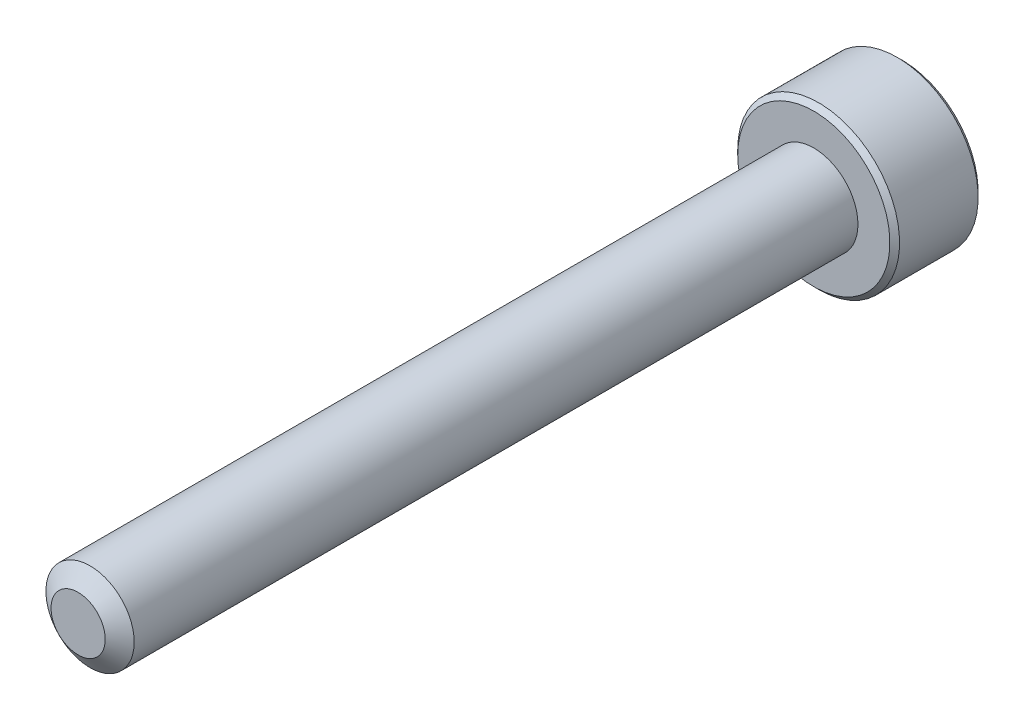
SolidWorks part; units mm, degrees
ref_plane "Front Plane" through (0, 0, 0) normal (0, 0, 1) x (1, 0, 0)
ref_plane "Top Plane" through (0, 0, 0) normal (0, 1, 0) x (1, 0, 0)
ref_plane "Right Plane" through (0, 0, 0) normal (1, 0, 0) x (0, 0, -1)
sketch "Sketch1" plane through (0, 0, 0) normal (0, 0, 1) x (1, 0, 0)
  circle A0 centre (0, 0) radius 1.5
  dimension "OD" = 3
extrude "Extrude1" add sketch "Sketch1" against normal blind 25
sketch "Sketch2" plane through (0, 0, 0) normal (0, 0, 1) x (1, 0, 0)
  circle A0 centre (0, 0) radius 1.5 construction
  circle A1 centre (0, 0) radius 1.5
curve "Helix/Spiral1" pitch 0.5 height 25.5 turns 51 parameters "pitch"=0.5
sketch "Sketch3" plane through (0, 0, 0) normal (1, 0, 0) x (0, 0, -1)
  line L0 (-0.4375, 1.5) -> (-0.25, 1.1752)
  line L1 (-0.25, 1.1752) -> (-0.1875, 1.1752)
  line L2 (-0.1875, 1.1752) -> (0, 1.5)
  line L3 (-0.4375, 1.5) -> (0, 1.5)
  line L4 (-0.2187, 1.5) -> (-0.2187, 1.1752) construction
  line L5 (-0.3437, 1.3376) -> (-0.0937, 1.3376) construction
  line L6 (0, 1.5) -> (0, -1.5) construction
  line L7 (0, -1.5) -> (25, -1.5) construction
  point P11 (2.25, -1.5)
  dimension "D1" = 0.0625
  dimension "D2" = 0.25
  dimension "D3" = 60
  dimension "D4" = 2.25
sweep "Cut-Sweep1" [suppressed] cut profiles "Sketch3" path "Helix/Spiral1"
sketch "Sketch4" plane through (0, 0, 0) normal (1, 0, 0) x (0, 0, -1)
  line L0 (0.4053, 1.5) -> (0, 0.9212)
  line L1 (0, 0.9212) -> (0, 1.5)
  line L2 (0.4053, 1.5) -> (0, 1.5)
  line L3 (-0.4375, 1.5) -> (0, 1.5) construction
  line L4 (0, 0) -> (7.0209, 0) construction
  dimension "D1" = 55
  dimension "D2" = 0.254
revolve "Cut-Revolve1" cut sketch "Sketch4" angle 360 about L4
sketch "Sketch5" [suppressed] plane through (0, 0, 0) normal (1, 0, 0) x (0, 0, -1)
  line L0 (25, -1.1822) -> (25, 1.0703) construction
  line L1 (25, 1.5) -> (18.1202, 1.5)
  line L2 (25, 1.5) -> (25, 0)
  line L3 (25, 0) -> (18, 0)
  line L4 (18, 1.1698) -> (18, 0)
  line L5 (18.1202, 1.5) -> (18, 1.1698)
  line L6 (0, 0) -> (9.9695, 0) construction
  point P3 (18, 1.5)
  point P10 (18, 1.5)
  dimension "D1" = 0.3302
  dimension "Thread min" = 18
  dimension "D3" = 20
revolve "partially thread" [suppressed] add sketch "Sketch5" angle 360 about L6
sketch "Sketch6" plane through (0, 0, -25) normal (0, 0, -1) x (-1, 0, 0)
  circle A0 centre (0, 0) radius 2.75
  dimension "head dia" = 5.5
extrude "Extrude2" add sketch "Sketch6" along normal blind 3
sketch "Sketch7" plane through (0, 0, -28) normal (0, 0, -1) x (-1, 0, 0)
  line L1 (0, 1.4434) -> (-1.25, 0.7217)
  line L2 (-1.25, 0.7217) -> (-1.25, -0.7217)
  line L3 (-1.25, -0.7217) -> (0, -1.4434)
  line L4 (0, -1.4434) -> (1.25, -0.7217)
  line L5 (1.25, -0.7217) -> (1.25, 0.7217)
  line L6 (1.25, 0.7217) -> (0, 1.4434)
  circle A0 centre (0, 0) radius 1.25 construction
  dimension "hex dia" = 2.5
extrude "Cut-Extrude1" cut sketch "Sketch7" against normal blind 1.875
sketch "Sketch8" plane through (0, 0, -28) normal (0, 0, -1) x (-1, 0, 0)
  circle A0 centre (0, 0) radius 1.4434
extrude "Cut-Extrude2" cut sketch "Sketch8" against normal through all draft 45
chamfer "Chamfer1" distance 0.165 angle 45 2 edges at (-2.75, 0, -28) (-2.75, 0, -25)
sketch "Sketch9" plane through (0, 0, 0) normal (1, 0, 0) x (0, 0, -1)
  line L0 (0, 1.5) -> (0, -1.5) construction
  line L1 (2.75, 1.5) -> (2.75, -1.5) construction
  dimension "D1" = 2.75
sketch "Sketch10" plane through (0, 0, 0) normal (1, 0, 0) x (0, 0, -1)
  line L0 (25, 1.5) -> (25, 0)
  line L1 (25, 1.5) -> (24.875, 1.5)
  line L2 (24.875, 1.5) -> (24.2537, 0)
  line L3 (25, 0) -> (24.2537, 0)
  line L4 (25, 2.585) -> (25, -2.585) construction
  dimension "D1" = 22.5
  dimension "D2" = 0.125
revolve "Revolve1" add sketch "Sketch10" angle 360 about L3
equation "\"D3@Helix/Spiral1\" = \"screw length@Extrude1\"+\"pitch@Helix/Spiral1\""
equation "\"D1@Sketch3\" = \"pitch@Helix/Spiral1\"*.125"
equation "\"D2@Sketch3\" = \"pitch@Helix/Spiral1\"*.5"
equation "\"D1@Cut-Extrude1\" = \"hex dia@Sketch7\"*.75"
equation "\"D1@Chamfer1\" = \"head dia@Sketch6\"*.03"
equation "\"D1@Sketch9\" = \"pitch@Helix/Spiral1\"*5.5"
equation "\"D2@Sketch10\" = \"pitch@Helix/Spiral1\"*.25"
equation "\"D4@Sketch3\" = \"pitch@Helix/Spiral1\"*4.50"
